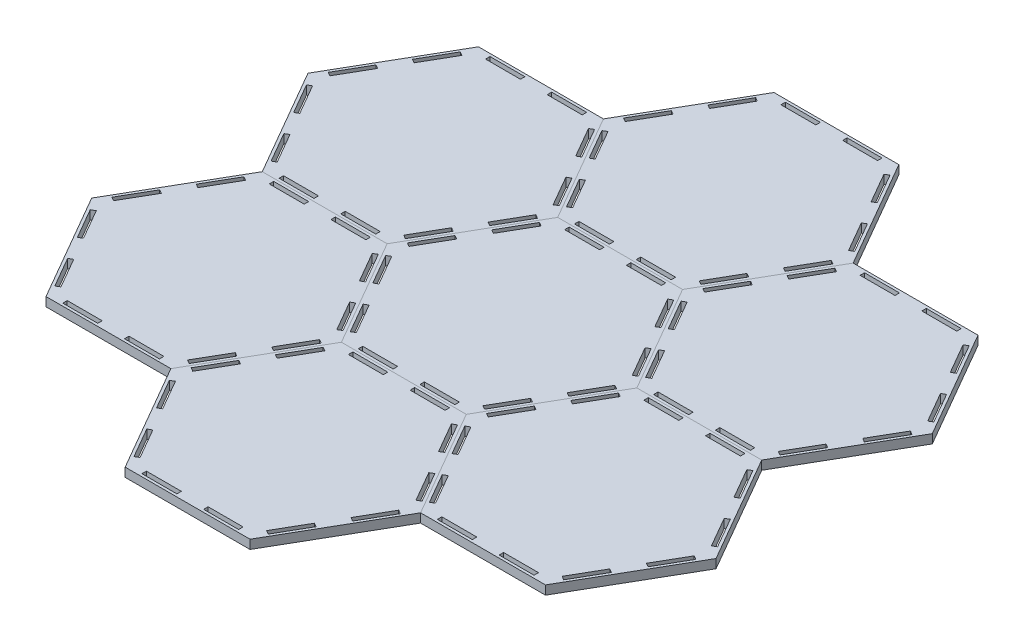
SolidWorks part; units mm, degrees
material "Cedar"
ref_plane "Front Plane" through (0, 0, 0) normal (0, 0, 1) x (1, 0, 0)
ref_plane "Top Plane" through (0, 0, 0) normal (0, 1, 0) x (1, 0, 0)
ref_plane "Right Plane" through (0, 0, 0) normal (1, 0, 0) x (0, 0, -1)
sketch "Sketch1" plane through (0, 0, 0) normal (0, 1, 0) x (1, 0, 0)
  line L0 (-88.9, 0) -> (-44.45, -76.9897)
  line L1 (88.9, 0) -> (44.45, 76.9897)
  line L2 (44.45, 76.9897) -> (-44.45, 76.9897)
  line L3 (-44.45, 76.9897) -> (-88.9, 0)
  line L4 (-44.45, -76.9897) -> (44.45, -76.9897)
  line L5 (44.45, -76.9897) -> (88.9, 0)
  line L6 (0, 0) -> (88.9, 0) construction
  circle A0 centre (0, 0) radius 76.9897 construction
  dimension "D1" = 88.9
extrude "Boss-Extrude1" add sketch "Sketch1" along normal blind 6.35
sketch "Sketch2" plane through (0, 6.35, 0) normal (0, 1, 0) x (1, 0, 0)
  line L0 (0, 0) -> (0, 58.6588) construction
  line L1 (50.8, -29.3294) -> (0, 58.6588) construction
  line L2 (0, 58.6588) -> (-50.8, -29.3294) construction
  line L3 (-50.8, -29.3294) -> (50.8, -29.3294) construction
  line L4 (-85.9671, 5.08) -> (-38.5841, -76.9897) construction
  line L5 (-44.45, 76.9897) -> (-88.9, 0) construction
  line L6 (-44.45, -76.9897) -> (44.45, -76.9897) construction
  line L7 (-88.9, 0) -> (-44.45, -76.9897) construction
  line L8 (-66.675, -38.4948) -> (-62.2756, -35.9548) construction
  line L9 (-79.4841, -6.1488) -> (-82.2337, -7.7363)
  line L10 (-82.2337, -7.7363) -> (-69.7877, -29.2934)
  line L11 (-69.7877, -29.2934) -> (-67.0381, -27.7059)
  line L12 (-67.0381, -27.7059) -> (-79.4841, -6.1488)
  line L13 (-45.0671, -65.7608) -> (-47.8167, -67.3483)
  line L14 (-57.5131, -44.2037) -> (-45.0671, -65.7608)
  line L15 (-47.8167, -67.3483) -> (-60.2627, -45.7912)
  line L16 (-60.2627, -45.7912) -> (-57.5131, -44.2037)
  line L17 (-38.5841, 76.9897) -> (-85.9671, -5.08) construction
  line L18 (-45.0671, 65.7608) -> (-47.8167, 67.3483)
  line L19 (-47.8167, 67.3483) -> (-60.2627, 45.7912)
  line L20 (-57.5131, 44.2037) -> (-45.0671, 65.7608)
  line L21 (-60.2627, 45.7912) -> (-57.5131, 44.2037)
  line L22 (-66.675, 38.4948) -> (-62.2756, 35.9548) construction
  line L23 (-69.7877, 29.2934) -> (-67.0381, 27.7059)
  line L24 (-82.2337, 7.7363) -> (-69.7877, 29.2934)
  line L25 (-67.0381, 27.7059) -> (-79.4841, 6.1488)
  line L26 (-79.4841, 6.1488) -> (-82.2337, 7.7363)
  line L27 (47.3829, 71.9097) -> (-47.3829, 71.9097) construction
  line L28 (34.417, 71.9097) -> (34.417, 75.0847)
  line L29 (34.417, 75.0847) -> (9.525, 75.0847)
  line L30 (9.525, 71.9097) -> (34.417, 71.9097)
  line L31 (9.525, 75.0847) -> (9.525, 71.9097)
  line L32 (0, 76.9897) -> (0, 71.9097) construction
  line L33 (-9.525, 75.0847) -> (-9.525, 71.9097)
  line L34 (-34.417, 75.0847) -> (-9.525, 75.0847)
  line L35 (-9.525, 71.9097) -> (-34.417, 71.9097)
  line L36 (-34.417, 71.9097) -> (-34.417, 75.0847)
  line L37 (85.9671, -5.08) -> (38.5841, 76.9897) construction
  line L38 (79.4841, 6.1488) -> (82.2337, 7.7363)
  line L39 (82.2337, 7.7363) -> (69.7877, 29.2934)
  line L40 (67.0381, 27.7059) -> (79.4841, 6.1488)
  line L41 (69.7877, 29.2934) -> (67.0381, 27.7059)
  line L42 (66.675, 38.4948) -> (62.2756, 35.9548) construction
  line L43 (60.2627, 45.7912) -> (57.5131, 44.2037)
  line L44 (47.8167, 67.3483) -> (60.2627, 45.7912)
  line L45 (57.5131, 44.2037) -> (45.0671, 65.7608)
  line L46 (45.0671, 65.7608) -> (47.8167, 67.3483)
  line L47 (38.5841, -76.9897) -> (85.9671, 5.08) construction
  line L48 (45.0671, -65.7608) -> (47.8167, -67.3483)
  line L49 (47.8167, -67.3483) -> (60.2627, -45.7912)
  line L50 (57.5131, -44.2037) -> (45.0671, -65.7608)
  line L51 (60.2627, -45.7912) -> (57.5131, -44.2037)
  line L52 (66.675, -38.4948) -> (62.2756, -35.9548) construction
  line L53 (69.7877, -29.2934) -> (67.0381, -27.7059)
  line L54 (82.2337, -7.7363) -> (69.7877, -29.2934)
  line L55 (67.0381, -27.7059) -> (79.4841, -6.1488)
  line L56 (79.4841, -6.1488) -> (82.2337, -7.7363)
  line L57 (-47.3829, -71.9097) -> (47.3829, -71.9097) construction
  line L58 (-34.417, -71.9097) -> (-34.417, -75.0847)
  line L59 (-34.417, -75.0847) -> (-9.525, -75.0847)
  line L60 (-9.525, -71.9097) -> (-34.417, -71.9097)
  line L61 (-9.525, -75.0847) -> (-9.525, -71.9097)
  line L62 (0, -76.9897) -> (0, -71.9097) construction
  line L63 (9.525, -75.0847) -> (9.525, -71.9097)
  line L64 (34.417, -75.0847) -> (9.525, -75.0847)
  line L65 (9.525, -71.9097) -> (34.417, -71.9097)
  line L66 (34.417, -71.9097) -> (34.417, -75.0847)
  circle A0 centre (0, 0) radius 29.3294 construction
  point P13 (0, 0)
  point P92 (0, 0)
  point P94 (0, 0)
  dimension "D1" = 101.6
  dimension "D4" = 5.08
  dimension "D5" = 3.175
  dimension "D6" = 24.892
  dimension "D7" = 9.525
  dimension "D8" = 6
extrude "Cut-Extrude1" cut sketch "Sketch2" against normal through all
ref_axis "Axis1" through (0, 0, 0) along (0, 1, 0)
mirror "Mirror1" about plane through (44.45, 6.35, 76.9897) normal (-0.866, 0, -0.5) of bodies 102
pattern_circular "CirPattern1" count 6 over 360 about axis through (0, 0, 0) along (0, 1, 0) of bodies 103
